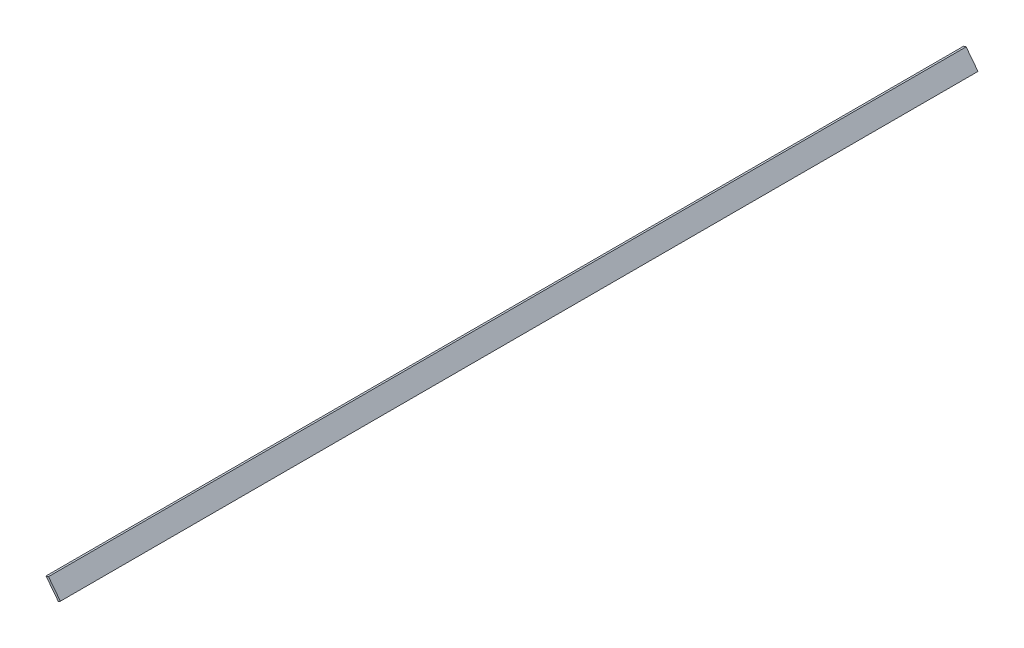
SolidWorks part; units mm, degrees
ref_plane "Front Plane" through (0, 0, 0) normal (0, 0, 1) x (1, 0, 0)
ref_plane "Top Plane" through (0, 0, 0) normal (0, 1, 0) x (1, 0, 0)
ref_plane "Right Plane" through (0, 0, 0) normal (1, 0, 0) x (0, 0, -1)
sketch "Sketch1" plane through (0, 0, 0) normal (0, 0, 1) x (1, 0, 0)
  line L0 (0, 0) -> (1.8691, 1.4444)
  line L1 (1.8691, 1.4444) -> (-9.8024, 16.5477)
  line L2 (-9.8024, 16.5477) -> (-12.2698, 15.8775)
  line L3 (-12.2698, 15.8775) -> (0, 0)
  dimension "D1" = 2.3622
  dimension "D2" = 67.5
  dimension "D3" = 90
  dimension "D4" = 20.066
extrude "Boss-Extrude1" add sketch "Sketch1" along normal blind 901.7
